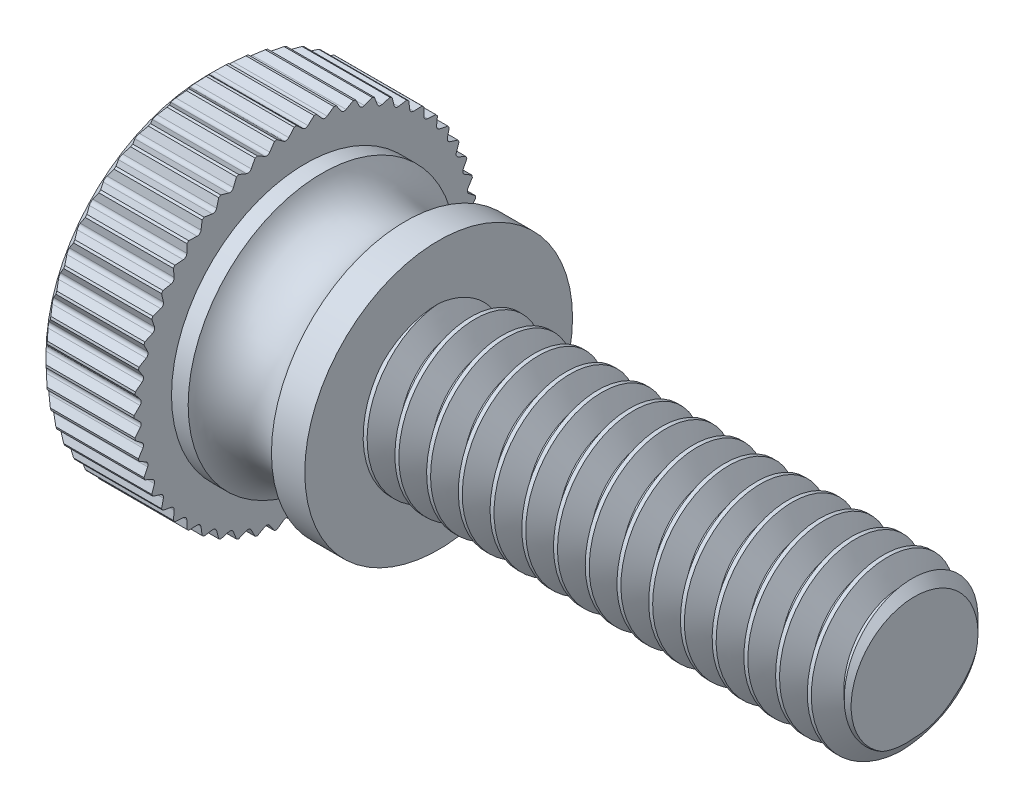
SolidWorks part; units mm, degrees
ref_plane "Front Plane" through (0, 0, 0) normal (0, 0, 1) x (1, 0, 0)
ref_plane "Top Plane" through (0, 0, 0) normal (0, 1, 0) x (1, 0, 0)
ref_plane "Right Plane" through (0, 0, 0) normal (1, 0, 0) x (0, 0, -1)
sketch "Sketch1" plane through (0, 0, 0) normal (0, 0, 1) x (1, 0, 0)
  line L0 (0, 0) -> (19.05, 0) construction
  line L1 (0, 0) -> (-9.271, 0) construction
  line L2 (-9.271, 6.858) -> (-9.271, -6.858) construction
  line L3 (19.05, 3.175) -> (19.05, -3.175) construction
  line L4 (0, 3.175) -> (0, -3.175) construction
  line L5 (-5.334, 5.3594) -> (-5.334, -5.3594) construction
  line L6 (-9.271, 6.858) -> (-5.334, 6.858) construction
  line L7 (19.05, 3.175) -> (17.78, 3.175) construction
  line L8 (-5.334, 5.3594) -> (0, 5.3594) construction
  line L9 (0, 3.175) -> (19.05, 3.175) construction
  line L10 (-9.271, -6.858) -> (-5.334, -6.858) construction
  line L11 (-5.334, -5.3594) -> (0, -5.3594) construction
  point P7 (19.05, 0)
  point P8 (0, 0)
  point P9 (-9.271, 0)
  point P16 (15.875, -3.175)
  point P17 (0, 0)
  point P21 (19.05, 0)
  point P22 (-9.271, 0)
  point P23 (-5.334, 0)
  dimension "Head Diameter" = 13.716
  dimension "Head Height" = 3.937
  dimension "Collar Diameter" = 10.7188
  dimension "Length" = 19.05
  dimension "Thread Pitch" = 1.27
  dimension "D2" = 3.175
  dimension "Overall Head Height" = 9.271
  dimension "Collar Height" = 5.334
  dimension "Screw Size Decimal Equivalent" = 6.35
sketch "Sketch2" plane through (0, 0, 0) normal (1, 0, 0) x (0, 0, -1)
  line L0 (0, 5.3594) -> (0, -5.3594) construction
  line L1 (-6.858, 0) -> (6.858, 0) construction
  line L2 (0, 6.858) -> (0, -6.858) construction
  circle A0 centre (0, 0) radius 6.858 construction
  circle A1 centre (0, 0) radius 5.3594 construction
  circle A2 centre (0, 0) radius 3.175 construction
  point P13 (0, -3.175)
  point P14 (3.175, 0)
  point P16 (0, 3.175)
  point P17 (-3.175, 0)
  point P18 (-5.3594, 0)
  point P19 (0, 5.3594)
  point P20 (5.3594, 0)
  point P21 (0, -5.3594)
  point P23 (0, -6.858)
  point P24 (6.858, 0)
  point P25 (0, 6.858)
  point P26 (-6.858, 0)
  point P27 (0, 0)
sketch "Sketch3" plane through (0, 0, 0) normal (0, 0, 1) x (1, 0, 0)
  line L0 (-9.271, 0) -> (-9.271, 6.858)
  line L1 (-9.271, 6.858) -> (-5.334, 6.858)
  line L2 (-5.334, 6.858) -> (-5.334, 5.3594)
  line L3 (-5.334, 5.3594) -> (-5.334, -5.3594) construction
  line L4 (-1.3335, 5.3594) -> (0, 5.3594)
  line L5 (0, -5.3594) -> (0, 5.3594) construction
  line L6 (0, 5.3594) -> (0, 3.175)
  line L7 (0, 3.175) -> (19.05, 3.175)
  line L8 (0, 3.175) -> (19.05, 3.175) construction
  line L10 (19.05, 3.175) -> (19.05, -3.175) construction
  line L11 (19.05, 3.175) -> (19.05, 0)
  line L12 (19.05, 0) -> (-9.271, 0)
  line L13 (-5.334, 5.3594) -> (-4.6673, 5.3594)
  line L14 (-5.334, 5.3594) -> (0, 5.3594) construction
  line L15 (-3.0004, 4.2875) -> (-3.0004, 5.3594) construction
  arc A1 (-4.6673, 5.3594) -> (-1.3335, 5.3594) centre (-3.0004, 6.1195) ccw
  dimension "D1" = 0.6667
  dimension "D2" = 1.3335
  dimension "D3" = 1.0719
revolve "Revolve1" add sketch "Sketch3" angle 360 about L0
chamfer "Chamfer1" distance 0.635 angle 45 1 edges at (19.05, 0, 3.175)
chamfer "Chamfer2" distance 0.4115 angle 45 1 edges at (-9.271, 0, 6.858)
split "Split1" trim tools "Right Plane" bodies to split 104 resulting bodies 105 106
sketch "Sketch4" plane through (19.05, 0, 0) normal (1, 0, 0) x (0, 0, -1)
  circle A0 centre (0, 0) radius 3.175
curve "Helix/Spiral1" pitch 1.27 height 20.32 turns 16
sketch "Sketch5" plane through (0, 0, 0) normal (0, 0, 1) x (1, 0, 0)
  line L0 (18.9706, 3.3125) -> (20.2406, 3.3125) construction
  line L1 (20.2406, 3.3125) -> (19.6056, 2.2126) construction
  line L2 (19.6056, 2.2126) -> (18.9706, 3.3125) construction
  line L3 (19.0103, 3.2437) -> (20.2009, 3.2437) construction
  line L4 (19.05, 3.175) -> (20.1612, 3.175) construction
  line L5 (19.5262, 2.3501) -> (19.685, 2.3501) construction
  line L6 (19.6056, 2.2126) -> (19.6056, 2.3501) construction
  line L7 (19.6056, 3.175) -> (19.6056, 3.3125) construction
  line L8 (19.0103, 3.2437) -> (20.2009, 3.2437)
  line L9 (20.2009, 3.2437) -> (19.685, 2.3501)
  line L10 (19.685, 2.3501) -> (19.5262, 2.3501)
  line L11 (19.5262, 2.3501) -> (19.0103, 3.2437)
  point P12 (19.6056, 3.2437)
  dimension "D1" = 1.27
  dimension "D2" = 0.1588
sweep "Cut-Sweep1" cut profiles "Sketch5" path "Helix/Spiral1" align with end faces yes
sketch "Sketch6" plane through (0, 0, 0) normal (1, 0, 0) x (0, 0, -1)
  circle A0 centre (0, 0) radius 3.175
  circle A1 centre (0, 0) radius 3.175 construction
extrude "Boss-Extrude1" add sketch "Sketch6" against normal through all draft 60
sketch "Sketch7" plane through (-9.271, 0, 0) normal (-1, 0, 0) x (0, 0, 1)
  line L0 (0, 0) -> (0.3594, 6.858) construction
  line L1 (0, 3.175) -> (0, -3.175) construction
  line L2 (0.3594, 6.858) -> (-0.3594, 6.858) construction
  line L3 (-0.3594, 6.858) -> (0, 0) construction
  line L4 (0, 0) -> (0, 6.858) construction
  line L5 (-0.6374, 7.112) -> (0.6374, 7.112)
  line L6 (0.6374, 7.112) -> (0, 6.5296) construction
  line L7 (0, 6.5296) -> (-0.6374, 7.112) construction
  line L8 (0, 6.5296) -> (0, 7.112) construction
  line L9 (-0.6374, 7.112) -> (-0.1029, 6.6236)
  line L10 (0.1029, 6.6236) -> (0.6374, 7.112)
  line L11 (0.1029, 6.6236) -> (-0.1029, 6.6236) construction
  line L12 (0, 6.858) -> (0, -6.858) construction
  circle A0 centre (0, 0) radius 6.858 construction
  arc A1 (-0.1029, 6.6236) -> (0.1029, 6.6236) centre (0, 6.7362) ccw
  point P16 (0, 6.5837)
  dimension "D1" = 6
  dimension "D2" = 0.2743
  dimension "D3" = 0.2057
  dimension "D4" = 0.254
extrude "Cut-Extrude1" cut sketch "Sketch7" against normal up to vertex (9.271 mm away) up to point (0, 6.858, 0)
pattern_circular "CirPattern1" count 54 over 360 about axis through (0, 0, 0) along (1, 0, 0) of "Cut-Extrude1"
equation "\"D2@Sketch1\"=\"Thread Pitch@Sketch1\"*2.5"
equation "\"D1@Sketch3\"=\"Collar Height@Sketch1\"*.125"
equation "\"D2@Sketch3\"=\"Collar Height@Sketch1\"*.25"
equation "\"D3@Sketch3\"=\"Collar Diameter@Sketch1\"*.1"
equation "\"D1@Chamfer1\"=\"Thread Pitch@Sketch1\"*.5"
equation "\"D1@Chamfer2\"=\"Head Diameter@Sketch1\"*.03"
equation "\"D4@Helix/Spiral1\"=\"Thread Pitch@Sketch1\""
equation "\"D3@Helix/Spiral1\"=\"Length@Sketch1\"+\"Thread Pitch@Sketch1\""
equation "\"D2@Sketch5\"=\"D1@Sketch5\"*.125"
equation "\"D1@Sketch5\"=\"Thread Pitch@Sketch1\""
equation "\"D2@Sketch7\"=\"Head Diameter@Sketch1\"*.02"
equation "\"D3@Sketch7\"=\"Head Diameter@Sketch1\"*.015"
equation "\"D1@CirPattern1\"=(360/\"D1@Sketch7\")*.9"
